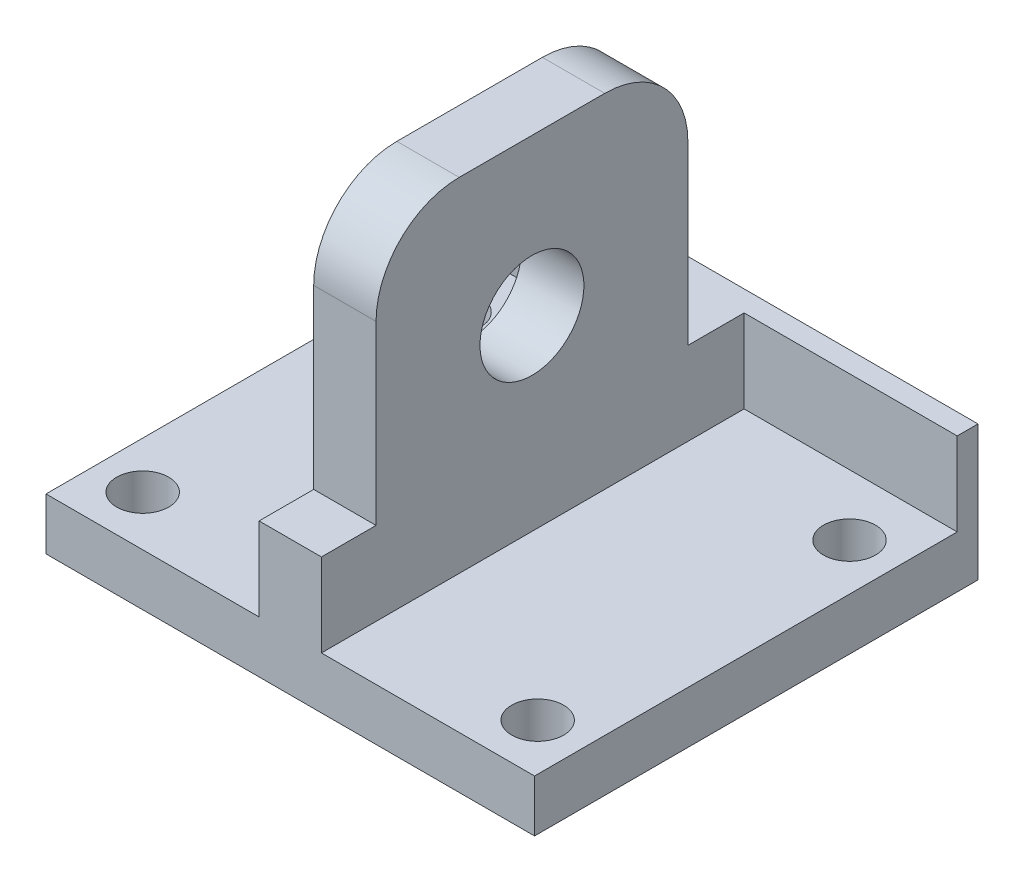
SolidWorks part; units mm, degrees
ref_plane "前视基准面" through (0, 0, 0) normal (0, 0, 1) x (1, 0, 0)
ref_plane "上视基准面" through (0, 0, 0) normal (0, 1, 0) x (1, 0, 0)
ref_plane "右视基准面" through (0, 0, 0) normal (1, 0, 0) x (0, 0, -1)
other "Configuration Table"
sketch "草图1" plane through (0, 0, 0) normal (0, 1, 0) x (1, 0, 0)
  line L1 (23.5, -12.9607) -> (-23.5, -12.9607)
  line L2 (23.5, -12.9607) -> (23.5, 29.7046)
  line L3 (23.5, 29.7046) -> (-23.5, 29.7046)
  line L4 (-23.5, -12.9607) -> (-23.5, 29.7046)
  circle A0 centre (-19, 21.8424) radius 2.5
  circle A1 centre (19, 21.8424) radius 2.5
  circle A2 centre (-19, -8.1576) radius 2.5
  circle A3 centre (19, -8.1576) radius 2.5
  point P0 (0, 0)
  dimension "D2" = 5
  dimension "D3" = 5
  dimension "D4" = 5
  dimension "D5" = 5
  dimension "D1" = 47
  dimension "D6" = 7.8621
extrude "凸台-拉伸1" add sketch "草图1" along normal blind 5 contours L4 L1 L2 L3 A3 A2 A1 A0 region at (0, 0, -8.4343)
sketch "草图2" plane through (0, 5, 0) normal (0, 1, 0) x (1, 0, 0)
  line L0 (23.5, 29.7046) -> (-23.5, 29.7046) construction
  line L1 (3, -12.9607) -> (-3, -12.9607)
  line L2 (3, -12.9607) -> (3, 29.7046)
  line L3 (3, 29.7046) -> (-3, 29.7046)
  line L4 (-3, -12.9607) -> (-3, 29.7046)
  line L5 (3, -12.9607) -> (-3, 29.7046) construction
  line L6 (3, 29.7046) -> (-3, -12.9607) construction
  line L7 (23.5, -12.9607) -> (-23.5, -12.9607) construction
  line L8 (0, 8.3719) -> (0, 0)
  line L9 (23.5, -12.9607) -> (23.5, 29.7046) construction
  line L10 (-23.5, 29.7046) -> (23.5, 29.7046)
  line L11 (-23.5, 29.7046) -> (-23.5, 27.7046)
  line L12 (-23.5, 27.7046) -> (23.5, 27.7046)
  line L13 (23.5, 29.7046) -> (23.5, 27.7046)
  point P0 (0, 8.3719)
  line M10 (-23.5, 29.7046) -> (-23.5, -12.9607)
  line M12 (23.5, -12.9607) -> (23.5, 29.7046)
  line M13 (23.5, 29.7046) -> (-23.5, 29.7046)
  dimension "D1" = 6
  dimension "D2" = 2
extrude "凸台-拉伸2" add sketch "草图2" along normal blind 33 contours L12 L4 L2 | L12 L4 M10 M13 | L2 L12 M12 M13 | L4 L12 L2 M13 region at (0, 5, 12.5497) region at (0, 5, -28.7046) region at (13.25, 5, -28.7046) region at (-13.25, 5, -28.7046)
sketch "草图3" plane through (-3, 0, 0) normal (-1, 0, 0) x (0, 0, 1)
  line L0 (-27.7046, 5) -> (12.9607, 5)
  point P8 (0, 0)
  line M3 (12.9607, 5) -> (12.9607, 38)
  line M4 (12.9607, 38) -> (-27.7046, 38)
  line M5 (-27.7046, 38) -> (-27.7046, 5)
extrude "凸台-拉伸3" add sketch "草图3" against normal up to surface (6 mm away) contours M4 | M4 | M4 | M4 | M4 | M3 M4 | M5 M4 | M4 M5 region at (-3, 21.5, -7.3719) up to face at (3, 21.5, -7.3719)
sketch "草图4" plane through (-3, 2.1172, 0) normal (-1, 0, 0) x (0, 0, 1)
  line L12 (-27.6221, 2.1767) -> (13.0432, 2.1767)
  line L13 (13.0432, 2.1767) -> (13.0432, 20.1767)
  line L16 (-29.6221, 20.1767) -> (-27.6221, 20.1767)
  line L17 (-27.6221, 20.1767) -> (-27.6221, 2.1767)
  line L18 (13.0432, 20.1767) -> (-2.9362, 26.9857)
  line L21 (-10.6523, 27.5823) -> (-29.6221, 20.1767)
  circle A0 centre (-7.2895, 20.8784) radius 5
  arc A5 (-2.9362, 26.9857) -> (-10.6523, 27.5823) centre (-7.2895, 20.8784) ccw
  point P6 (-7.2895, 20.4801)
  point P7 (-7.2895, 21.2422)
  dimension "D2" = 10
extrude "切除-拉伸2" cut sketch "草图4" against normal blind 7 contours A0 | A0 region at (-3, 22.9956, -7.2895)
chamfer "倒角1" distance 3 angle 45 2 edges at (23.5, 38, -28.7046) (-23.5, 38, -28.7046)
sketch "草图6" plane through (0, 38, 0) normal (0, 1, 0) x (1, 0, 0)
  line L0 (-3, 21.5525) -> (28.9873, 21.5525)
  line L1 (-3, -12.9607) -> (-3, 27.7046) construction
  line L2 (28.9873, 21.5525) -> (28.9873, 31.4157)
  line L3 (28.9873, 31.4157) -> (-26.3946, 31.4157)
  line L4 (-26.3946, 31.4157) -> (-26.3946, 21.5525)
  line L5 (-26.3946, 21.5525) -> (-3, 21.5525)
  line L6 (-26.3946, -7.7075) -> (28.7744, -7.7075)
  line L7 (28.7744, -7.7075) -> (28.7744, -30.2408)
  line L8 (28.7744, -30.2408) -> (-26.3946, -30.2408)
  line L9 (-26.3946, -30.2408) -> (-26.3946, -7.7075)
  line L10 (-26.3946, 22.2925) -> (28.9873, 22.2925)
  line L11 (-26.3946, 22.2925) -> (-26.3946, 21.5525)
  line M6 (3, 27.7046) -> (20.5, 27.7046)
  line M7 (20.5, 27.7046) -> (20.5, 29.7046)
  line M8 (20.5, 29.7046) -> (-20.5, 29.7046)
  line M9 (-20.5, 29.7046) -> (-20.5, 27.7046)
  line M10 (-20.5, 27.7046) -> (-3, 27.7046)
  line M11 (-3, 27.7046) -> (-3, -12.9607)
  line M12 (-3, -12.9607) -> (3, -12.9607)
  line M13 (3, -12.9607) -> (3, 27.7046)
  dimension "D1" = 0.74
  dimension "D2" = 30
extrude "切除-拉伸8" cut sketch "草图6" against normal blind 25 contours L4 L10 L2 L3 M11 M10 M9 M8 M7 M6 M13 | L10 M11 M13 M6 M7 M8 M9 M10 | L9 L8 L7 L6 M13 M12 M11 | L6 M11 M12 M13 region at (0, 38, -27.6533) region at (-14.6973, 38, -22.8538) region at (1.2209, 38, 19.1989) region at (0, 38, 10.3341)
fillet "圆角3" radius 8 2 edges at (0, 38, 7.7075) (0, 38, -22.2925)
